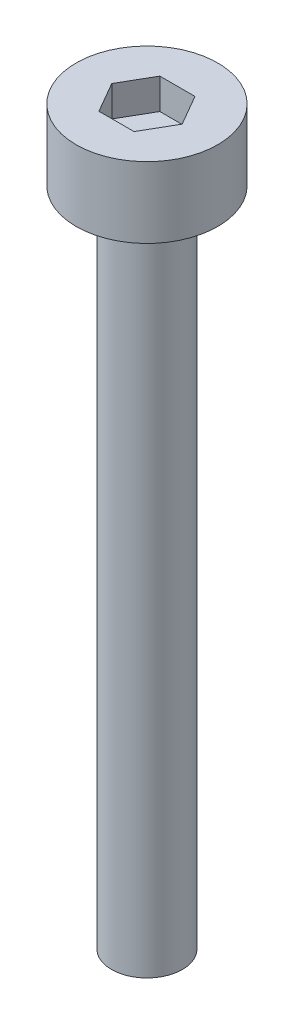
SolidWorks part; units mm, degrees
ref_plane "Front Plane" through (0, 0, 0) normal (0, 0, 1) x (1, 0, 0)
ref_plane "Top Plane" through (0, 0, 0) normal (0, 1, 0) x (1, 0, 0)
ref_plane "Right Plane" through (0, 0, 0) normal (1, 0, 0) x (0, 0, -1)
sketch "Sketch1" plane through (0, 0, 0) normal (0, 1, 0) x (1, 0, 0)
  circle A0 centre (0, 0) radius 1.5
  dimension "D1" = 3
extrude "ScrewShaft" add sketch "Sketch1" along normal blind 28
sketch "Sketch2" plane through (0, 28, 0) normal (0, 1, 0) x (1, 0, 0)
  circle A0 centre (0, 0) radius 3
  dimension "D1" = 6
extrude "Boss-Extrude2" add sketch "Sketch2" along normal blind 3
sketch "Sketch3" plane through (0, 31, 0) normal (0, 1, 0) x (1, 0, 0)
  line L0 (0, 0) -> (0, 1.29) construction
  line L1 (1.4896, 0) -> (0.7448, 1.29)
  line L2 (0.7448, 1.29) -> (-0.7448, 1.29)
  line L3 (-0.7448, 1.29) -> (-1.4896, 0)
  line L4 (-1.4896, 0) -> (-0.7448, -1.29)
  line L5 (-0.7448, -1.29) -> (0.7448, -1.29)
  line L6 (0.7448, -1.29) -> (1.4896, 0)
  circle A0 centre (0, 0) radius 1.29 construction
  dimension "D1" = 2.58
extrude "Cut-Extrude1" cut sketch "Sketch3" against normal blind 1.3
equation "\"X-ROD-SPACING\"=45"
equation "\"Y-ROD-SPACING\"=75"
equation "\"Z-ROD-SPACING\"=17.5"
equation "\"Y-BED-OFFSET\"=2"
equation "\"Y-BED-ROD-INSET\"=3.5"
equation "\"T-SLOT-NUT-FILLET-RADIUS\"=0.5"
equation "\"T-SLOT-SCREW-SHAFT-RADIUS\"=1.55"
equation "\"T-SLOT-SCREW-SHAFT-CUTOUT-LENGTH\"=11.0"
equation "\"T-SLOT-NUT-DEPTH\"=3.5"
equation "\"T-SLOT-NUT-WIDTH\"=2.85"
equation "\"T-SLOT-NUT-END-DISTANCE\"=8"
equation "\"ACRYLIC-THICKNESS\"=10"
equation "\"ACRYLIC-THICKNESS2\"=4.5"
equation "\"ACRYLIC-TAB-CUTOUT-SIZE\"=\"ACRYLIC-THICKNESS\"+\"ACRYLIC-TAB-TOLERANCE\"*2"
equation "\"ACRYLIC-TAB-WIDTH\"=\"ACRYLIC-THICKNESS\""
equation "\"ACRYLIC-M3-HOLE\"=2.9"
equation "\"SMOOTHROD-CAP-SCREW-DISTANCE\"=20"
equation "\"FRAME-WIDTH-INNER\"=370"
equation "\"NEMA17-HOLE-SPACING\"=31"
equation "\"NEMA17-CENTRAL-CUTOUT\"=22.5"
equation "\"Z-BRACKET-REACH\"=55"
equation "\"TOP-BRACKET-SPACING\"=40"
equation "\"SMOOTHROD-X-LENGTH\"=350"
equation "\"SMOOTHROD-Y-LENGTH\"=350"
equation "\"SMOOTHROD-Z-LENGTH\"=350"
equation "\"SMOOTHROD-TIGHTENING-HEADROOM\"=.25"
equation "\"LEADSCREW-Z-LENGTH\"=300"
equation "\"SCREW-LENGTH-FRAME\"=\"ACRYLIC-THICKNESS\" + 10"
equation "\"SCREW-HEAD-RADIUS\"=6"
equation "\"PRINTED-X-SMOOTHROD-DIAMETER\"=9.0"
equation "\"PRINTED-X-SMOOTHROD-CUTOUT\"=10"
equation "\"PRINTED-X-BASE-HEIGHT\"=10"
equation "\"PRINTED-LM8UU-CUTOUT-SIZE\"=15.5"
equation "\"PRINTED-LM8UU-CUTOUT-LENGTH\"=24.5"
equation "\"PRINTED-X-IDLER-HEIGHT\"=16"
equation "\"PSU-MOUNTING-WIDTH\"=95"
equation "\"PSU-MOUNTING-HEIGHT\"=177"
equation "\"D1@ScrewShaft\"=\"SCREW-LENGTH-EXTRUDER\""
equation "\"D1@Sketch2\"=\"SCREW-HEAD-RADIUS\""
equation "\"Y-BED-SCREW-SPACING\"=209"
equation "\"Y-BED-SCREW-CUTOUT-SLOT-HEIGHT\"=2"
equation "\"Z-ROD-INSET\"=16"
equation "\"SCREW-LENGTH-MOTOR\"=\"ACRYLIC-THICKNESS\" + 5"
equation "\"SCREW-LENGTH-EXTRUDER\"=28"
equation "\"Y-BELT-TO-ROD-DISTANCE\"=20"
equation "\"SPOOL-HOLDER-ROD-SPACING\"=150"
equation "\"ACRYLIC-X-CARRIAGE-WIDTH\"=55"
equation "\"ACRYLIC-X-CARRIAGE-HEIGHT\"=75"
equation "\"ACRYLIC-X-CARRIAGE-CENTER-TAB-SPACING\"=14"
